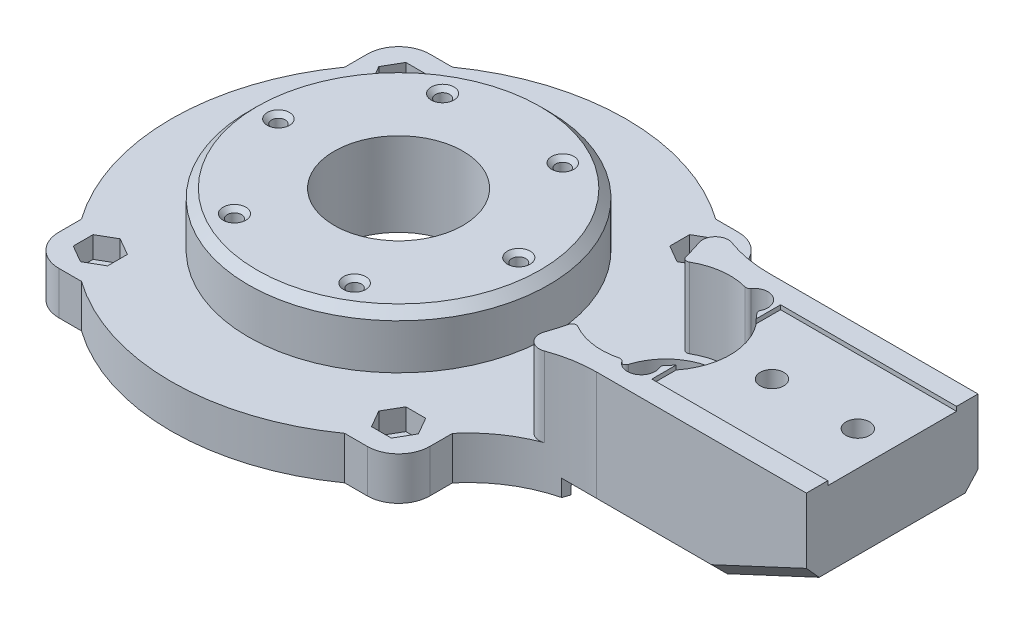
SolidWorks part; units mm, degrees
ref_plane "Front Plane" through (0, 0, 0) normal (0, 0, 1) x (1, 0, 0)
ref_plane "Top Plane" through (0, 0, 0) normal (0, 1, 0) x (1, 0, 0)
ref_plane "Right Plane" through (0, 0, 0) normal (1, 0, 0) x (0, 0, -1)
sketch "Sketch3" plane through (0, 0, 0) normal (0, -1, 0) x (1, 0, 0)
  line L1 (-28.2, -28.2) -> (28.2, -28.2) construction
  line L2 (-28.2, -28.2) -> (-28.2, 28.2) construction
  line L3 (-28.2, 28.2) -> (28.2, 28.2) construction
  line L4 (28.2, -28.2) -> (28.2, 28.2) construction
  line L5 (-28.2, -28.2) -> (28.2, 28.2) construction
  line L6 (-28.2, 28.2) -> (28.2, -28.2) construction
  circle A0 centre (0, 0) radius 62.5
  point P0 (0, 0)
  dimension "D2" = 125
  dimension "D1" = 56.4
extrude "Boss-Extrude3" add sketch "Sketch3" along normal blind 10
sketch "Sketch19" plane through (0, -10, 0) normal (0, -1, 0) x (1, 0, 0)
  line L0 (62.5, 0) -> (115, 0) construction
  line L1 (59.2136, -20) -> (115, -20)
  line L2 (59.2136, 20) -> (115, 20)
  line L3 (115, 20) -> (115, -20)
  line L4 (0, 20) -> (115, 20) construction
  line L5 (0, 0) -> (115, 0) construction
  line L6 (0, -20) -> (115, -20) construction
  circle A0 centre (0, 0) radius 62.5 construction
  arc A1 (59.2136, -20) -> (59.2136, 20) centre (0, 0) ccw
  dimension "D3" = 115
  dimension "D1" = 20
  dimension "D2" = 20
extrude "Boss-Extrude4" add sketch "Sketch19" against normal up to surface (10 mm away) up to face at (0, 0, -62.5)
sketch "Sketch20" plane through (0, 0, 0) normal (0, 1, 0) x (1, 0, 0)
  line L0 (0, 0) -> (119.1554, 0) construction
  line L6 (51.2348, -20) -> (115, -20)
  line L7 (115, -20) -> (115, 20)
  line L8 (115, 20) -> (51.2348, 20)
  arc A0 (51.2348, -20) -> (51.2348, 20) centre (0, 0) ccw
  dimension "D1" = 110
  dimension "D2" = 40
  dimension "D3" = 115
extrude "Boss-Extrude5" add sketch "Sketch20" along normal blind 18.5
chamfer "Chamfer1" distance 10 angle 65 1 edges at (115, -10, 0) first distance on face at (115, 4.25, 0)
sketch "Sketch21" plane through (0, -10, 0) normal (0, -1, 0) x (1, 0, 0)
  line L0 (115, 0) -> (0, 0) construction
  line L2 (115, 20) -> (115, -20) construction
  circle A0 centre (0, 0) radius 51 construction
  circle A1 centre (62.25, 0) radius 11.25 construction
  circle A2 centre (62.25, 0) radius 13
  dimension "D1" = 102
  dimension "D2" = 22.5
  dimension "D3" = 26
extrude "Cut-Extrude12" cut sketch "Sketch21" against normal blind 66
sketch "Sketch24" plane through (0, -10, 0) normal (0, -1, 0) x (1, 0, 0)
  circle A1 centre (62.25, 0) radius 13
  circle A2 centre (62.25, 0) radius 13
  dimension "D1" = 0
sketch "Sketch25" plane through (115, 0, 0) normal (1, 0, 0) x (0, 0, -1)
  line L0 (-20, 18.5) -> (20, 18.5) construction
  line L1 (15, 19.5) -> (-15, 19.5)
  line L2 (15, 19.5) -> (15, 17.5)
  line L3 (15, 17.5) -> (-15, 17.5)
  line L4 (-15, 19.5) -> (-15, 17.5)
  line L5 (15, 19.5) -> (-15, 17.5) construction
  line L6 (15, 17.5) -> (-15, 19.5) construction
  point P0 (0, 18.5)
  dimension "D1" = 2
  dimension "D2" = 30
extrude "Cut-Extrude14" cut sketch "Sketch25" against normal blind 41
sketch "Sketch26" plane through (0, -10, 0) normal (0, -1, 0) x (1, 0, 0)
  line L0 (115, 0) -> (0, 0) construction
  line L1 (115, 20) -> (115, -20) construction
  circle A0 centre (107, 0) radius 2.75
  circle A1 centre (87, 0) radius 2.75
  dimension "D3" = 5.5
  dimension "D1" = 8
  dimension "D2" = 20
extrude "Cut-Extrude15" cut sketch "Sketch26" against normal through all
sketch "Sketch27" plane through (0, -10, 0) normal (0, -1, 0) x (1, 0, 0)
  circle A0 centre (87, 0) radius 4.6
  circle A1 centre (107, 0) radius 4.6
  dimension "D1" = 9.2
extrude "Cut-Extrude16" cut sketch "Sketch27" against normal blind 14
chamfer "Chamfer3" distance 3 angle 45 4 edges at (104.2775, -5, -20) (76.3843, -10, -20) (104.2775, -5, 20) (76.3843, -10, 20)
sketch "Sketch43" plane through (0, -15, 0) normal (0, -1, 0) x (1, 0, 0)
  line L0 (62.25, 0) -> (47.2509, -0.1631) construction
  line L1 (62.25, 0) -> (69.6081, 13.0713) construction
  line L2 (62.25, 0) -> (69.8908, -12.9081) construction
  circle A0 centre (47.2509, -0.1631) radius 1.75
  circle A1 centre (69.6081, 13.0713) radius 1.75
  circle A2 centre (69.8908, -12.9081) radius 1.75
  circle A3 centre (62.25, 0) radius 15 construction
  dimension "D1" = 3.5
  dimension "D2" = 30
  dimension "D3" = 120.001
  dimension "D4" = 120
extrude "Cut-Extrude22" cut sketch "Sketch43" against normal blind 42
sketch "Sketch44" plane through (0, 0, 0) normal (0, 1, 0) x (1, 0, 0)
  circle A0 centre (69.8908, 12.9081) radius 3
  dimension "D1" = 6
extrude "Cut-Extrude23" cut sketch "Sketch44" against normal blind 5
sketch "Sketch49" plane through (0, 18.5, 0) normal (0, 1, 0) x (1, 0, 0)
  circle A0 centre (69.6081, -13.0713) radius 3.25
  circle A1 centre (47.2509, 0.1631) radius 3.25
  circle A2 centre (69.8908, 12.9081) radius 3.25
  dimension "D1" = 6.5
extrude "Cut-Extrude28" cut sketch "Sketch49" against normal blind 23
fillet "Fillet4" radius 1 2 edges at (49.4953, -2.25, -2.5136) (49.4437, -2.25, 2.2357)
chamfer "Chamfer6" distance 1 angle 45 3 edges at (69.8908, -5, -11.1581) (47.2509, -4.5, 1.5869) (69.6081, -4.5, 14.8213)
sketch "Sketch52" plane through (0, 18.5, 0) normal (0, 1, 0) x (1, 0, 0)
  circle A1 centre (0, 0) radius 49
  dimension "D1" = 98
sketch "Sketch53" plane through (0, 0, 0) normal (0, 1, 0) x (1, 0, 0)
  circle A0 centre (0, 0) radius 35
  dimension "D1" = 70
extrude "Boss-Extrude7" add sketch "Sketch53" along normal blind 12.5
sketch "Sketch54" plane through (0, -10, 0) normal (0, -1, 0) x (1, 0, 0)
  line L1 (-34.75, 34.75) -> (34.75, 34.75) construction
  line L2 (-34.75, 34.75) -> (-34.75, -34.75) construction
  line L3 (-34.75, -34.75) -> (34.75, -34.75) construction
  line L4 (34.75, 34.75) -> (34.75, -34.75) construction
  line L5 (-34.75, 34.75) -> (34.75, -34.75) construction
  line L6 (-34.75, -34.75) -> (34.75, 34.75) construction
  circle A0 centre (-34.75, 34.75) radius 2.75
  circle A1 centre (34.75, 34.75) radius 2.75
  circle A2 centre (34.75, -34.75) radius 2.75
  circle A3 centre (-34.75, -34.75) radius 2.75
  point P0 (0, 0)
  dimension "D2" = 5.5
  dimension "D1" = 69.5
extrude "Cut-Extrude29" cut sketch "Sketch54" against normal through all
chamfer "Chamfer7" distance 2 angle 45 1 edges at (0, 12.5, 35)
sketch "Sketch56" plane through (0, -10, 0) normal (0, -1, 0) x (1, 0, 0)
  line L2 (-35.925, -42.925) -> (35.925, -42.925)
  line L6 (42.925, -35.925) -> (42.925, 35.925)
  line L10 (35.925, 42.925) -> (-35.925, 42.925)
  line L14 (-42.925, 35.925) -> (-42.925, -35.925)
  circle A0 centre (0, 0) radius 37
  circle A1 centre (-34.75, 34.75) radius 2.75
  circle A2 centre (34.75, 34.75) radius 2.75
  circle A3 centre (-34.75, -34.75) radius 2.75
  circle A4 centre (34.75, -34.75) radius 2.75
  arc A5 (-42.925, -35.925) -> (-35.925, -42.925) centre (-35.925, -35.925) ccw
  arc A7 (35.925, -42.925) -> (42.925, -35.925) centre (35.925, -35.925) ccw
  arc A9 (42.925, 35.925) -> (35.925, 42.925) centre (35.925, 35.925) ccw
  arc A11 (-35.925, 42.925) -> (-42.925, 35.925) centre (-35.925, 35.925) ccw
  dimension "D1" = 74
sketch "Sketch57" plane through (0, -10, 0) normal (0, -1, 0) x (1, 0, 0)
  line L0 (35.925, 42.925) -> (-35.925, 42.925) construction
  line L1 (-42.925, 35.925) -> (-42.925, -35.925) construction
  line L2 (42.925, -35.925) -> (42.925, 35.925) construction
  line L3 (60.1436, -17) -> (93.5549, -17)
  line L4 (93.5549, -17) -> (93.5549, 17)
  line L5 (93.5549, 17) -> (60.1436, 17)
  line L7 (93.5549, -17) -> (93.5549, 17)
  line L8 (93.5549, 17) -> (60.1436, 17)
  line L9 (-35.925, -42.925) -> (35.925, -42.925) construction
  line L10 (35.925, 42.925) -> (-35.925, 42.925) construction
  line L11 (-42.925, 35.925) -> (-42.925, -35.925) construction
  line L12 (42.925, -35.925) -> (42.925, 35.925) construction
  line L13 (-35.925, -42.925) -> (35.925, -42.925) construction
  line L14 (35.925, 43.225) -> (-35.925, 43.225)
  line L15 (-43.225, 35.925) -> (-43.225, -35.925)
  line L16 (-35.925, -43.225) -> (35.925, -43.225)
  line L17 (43.225, -35.925) -> (43.225, 35.925)
  line L21 (60.1436, -17) -> (93.5549, -17)
  arc A0 (-35.925, 42.925) -> (-42.925, 35.925) centre (-35.925, 35.925) ccw construction
  arc A1 (-42.925, -35.925) -> (-35.925, -42.925) centre (-35.925, -35.925) ccw construction
  arc A2 (35.925, -42.925) -> (42.925, -35.925) centre (35.925, -35.925) ccw construction
  arc A3 (60.1436, 17) -> (60.1436, -17) centre (0, 0) ccw
  arc A4 (60.1436, 17) -> (60.1436, -17) centre (0, 0) ccw
  arc A9 (-35.925, 42.925) -> (-42.925, 35.925) centre (-35.925, 35.925) ccw construction
  arc A10 (-42.925, -35.925) -> (-35.925, -42.925) centre (-35.925, -35.925) ccw construction
  arc A11 (35.925, -42.925) -> (42.925, -35.925) centre (35.925, -35.925) ccw construction
  arc A12 (42.925, 35.925) -> (35.925, 42.925) centre (35.925, 35.925) ccw construction
  arc A13 (42.925, 35.925) -> (35.925, 42.925) centre (35.925, 35.925) ccw construction
  arc A14 (-35.925, 43.225) -> (-43.225, 35.925) centre (-35.925, 35.925) ccw
  arc A15 (-43.225, -35.925) -> (-35.925, -43.225) centre (-35.925, -35.925) ccw
  arc A16 (35.925, -43.225) -> (43.225, -35.925) centre (35.925, -35.925) ccw
  arc A17 (43.225, 35.925) -> (35.925, 43.225) centre (35.925, 35.925) ccw
  dimension "D1" = 0
  dimension "D2" = 0.3
sketch "Sketch61" plane through (0, 0, 0) normal (0, 1, 0) x (1, 0, 0)
  circle A0 centre (34.75, -34.75) radius 5.5
  circle A1 centre (-34.75, -34.75) radius 5.5
  circle A2 centre (-34.75, 34.75) radius 5.5
  circle A3 centre (34.75, 34.75) radius 5.5
  dimension "D1" = 11
fillet "Fillet6" radius 1 4 edges at (70.8042, 7, -9.789) (66.717, 7, -12.2084) (70.5891, 7, 9.9729) (66.4502, 7, 12.3028)
sketch "Sketch66" plane through (0, 18.5, 0) normal (0, 1, 0) x (1, 0, 0)
  circle A0 centre (62.25, 0) radius 15
  dimension "D1" = 30
extrude "Cut-Extrude39" cut sketch "Sketch66" against normal up to surface (18.5 mm away) up to face at (-34.75, 0, -37.5)
sketch "Sketch67" plane through (0, -10, 0) normal (0, -1, 0) x (1, 0, 0)
  line L4 (-35.925, -43.225) -> (-30.6692, -43.225)
  line L5 (43.225, -35.925) -> (43.225, -30.6692)
  line L6 (35.925, 43.225) -> (30.6692, 43.225)
  line L7 (-43.225, 35.925) -> (-43.225, 30.6692)
  line L8 (-30.6692, 43.225) -> (-35.925, 43.225)
  line L9 (-43.225, -30.6692) -> (-43.225, -35.925)
  line L10 (30.6692, -43.225) -> (35.925, -43.225)
  line L11 (43.225, 30.6692) -> (43.225, 35.925)
  line L12 (59.2136, -20) -> (49.0816, -20)
  line L13 (51.2348, 20) -> (49.0816, 20)
  line L19 (115, 20) -> (51.2348, 20)
  line L20 (115, 15) -> (115, 20)
  line L21 (74, 15) -> (115, 15)
  line L22 (74, 9.324) -> (74, 15)
  line L26 (59.2136, 20) -> (51.2348, 20)
  arc A0 (-43.225, 30.6692) -> (-43.225, -30.6692) centre (0, 0) ccw
  arc A5 (-43.225, -35.925) -> (-35.925, -43.225) centre (-35.925, -35.925) ccw
  arc A6 (35.925, -43.225) -> (43.225, -35.925) centre (35.925, -35.925) ccw
  arc A7 (43.225, 35.925) -> (35.925, 43.225) centre (35.925, 35.925) ccw
  arc A8 (-35.925, 43.225) -> (-43.225, 35.925) centre (-35.925, 35.925) ccw
  arc A9 (43.225, -30.6692) -> (49.0816, -20) centre (0, 0) ccw
  arc A10 (-30.6692, -43.225) -> (30.6692, -43.225) centre (0, 0) ccw
  arc A11 (30.6692, 43.225) -> (-30.6692, 43.225) centre (0, 0) ccw
  arc A12 (59.2136, 20) -> (59.2136, -20) centre (0, 0) ccw construction
  arc A13 (59.2136, 20) -> (59.2136, -20) centre (0, 0) ccw
  arc A14 (49.0816, 20) -> (43.225, 30.6692) centre (0, 0) ccw
  arc A19 (74, 9.324) -> (72.2508, 11.1796) centre (62.25, 0) ccw
  arc A22 (72.2508, 11.1796) -> (66.6199, 14.3494) centre (69.6081, 13.0713) ccw
  arc A23 (66.6199, 14.3494) -> (53.615, 12.2652) centre (62.25, 0) ccw
  arc A24 (53.615, 12.2652) -> (51.2348, 20) centre (0, 0) ccw
  point P28 (58.3572, -20)
  point P30 (0, 0)
  dimension "D1" = 0
extrude "Cut-Extrude40" cut sketch "Sketch67" against normal through all
fillet "Fillet8" radius 30 2 edges at (49.0816, -5, 20) (49.0816, -5, -20)
fillet "Fillet9" radius 3 2 edges at (48.6585, 9.25, 25.6389) (48.6585, 9.25, -25.6389)
fillet "Fillet10" radius 1 6 edges at (72.4918, 9.25, -10.9593) (66.9312, 9.25, -14.2508) (53.615, 9.25, -12.2652) (53.615, 9.25, 12.2652) (66.6199, 9.25, 14.3494) (72.2508, 9.25, 11.1796)
sketch "Sketch68" plane through (0, -10, 0) normal (0, -1, 0) x (1, 0, 0)
  circle A0 centre (62.25, 0) radius 19.5
  dimension "D1" = 39
extrude "Cut-Extrude41" cut sketch "Sketch68" against normal blind 2
sketch "Sketch70" plane through (0, -10, 0) normal (0, -1, 0) x (1, 0, 0)
  circle A1 centre (0, 0) radius 37
  circle A2 centre (0, 0) radius 37
  dimension "D1" = 0
extrude "Cut-Extrude42" cut sketch "Sketch70" against normal blind 3
sketch "Sketch71" plane through (0, -10, 0) normal (0, -1, 0) x (1, 0, 0)
  circle A0 centre (0, 0) radius 15
extrude "Cut-Extrude43" cut sketch "Sketch71" against normal through all
sketch "Sketch73" plane through (0, 12.5, 0) normal (0, 1, 0) x (1, 0, 0)
  circle A0 centre (0, 0) radius 28 construction
  circle A1 centre (-28, 0) radius 1.6
  circle A2 centre (14, 24.2487) radius 1.6
  circle A3 centre (14, -24.2487) radius 1.6
  point P12 (0, 0)
  dimension "D1" = 56
  dimension "D2" = 3.2
  dimension "D3" = 3
extrude "Cut-Extrude44" cut sketch "Sketch73" against normal blind 6
sketch "Sketch74" plane through (0, 12.5, 0) normal (0, 1, 0) x (1, 0, 0)
  line L0 (0, 0) -> (-19.4633, 33.7115) construction
  line L1 (0, 0) -> (-28, 0) construction
  circle A0 centre (0, 0) radius 28 construction
  circle A1 centre (-14, 24.2487) radius 1.65
  point P8 (0, 0)
  dimension "D2" = 3.3
  dimension "D1" = 60
extrude "Cut-Extrude45" cut sketch "Sketch74" against normal through all
sketch "Sketch75" plane through (0, -10, 0) normal (0, -1, 0) x (1, 0, 0)
  line L1 (-15.5484, -27.0211) -> (-12.3733, -26.9758)
  line L2 (-12.3733, -26.9758) -> (-10.8249, -24.2035)
  line L3 (-10.8249, -24.2035) -> (-12.4516, -21.4764)
  line L4 (-12.4516, -21.4764) -> (-15.6267, -21.5216)
  line L5 (-15.6267, -21.5216) -> (-17.1751, -24.294)
  line L6 (-17.1751, -24.294) -> (-15.5484, -27.0211)
  circle A0 centre (-14, -24.2487) radius 2.75 construction
  dimension "D1" = 5.5
extrude "Cut-Extrude46" cut sketch "Sketch75" against normal blind 14
pattern_circular "CirPattern1" count 3 over 360 about axis through (0, -7, 0) along (0, -1, 0) of "Cut-Extrude46", "Cut-Extrude45"
chamfer "Chamfer8" distance 1 angle 45 6 edges at (-12.5711, 12.5, 23.4237) (-28, 12.5, 1.6) (-14, 12.5, -22.5987) (14, 12.5, -22.6487) (26.5711, 12.5, -0.825) (14, 12.5, 25.8487)
sketch "Sketch76" plane through (0, 0, 0) normal (0, 1, 0) x (1, 0, 0)
  line L1 (-34.75, -39.3688) -> (-30.75, -37.0594)
  line L2 (-30.75, -37.0594) -> (-30.75, -32.4406)
  line L3 (-30.75, -32.4406) -> (-34.75, -30.1312)
  line L4 (-34.75, -30.1312) -> (-38.75, -32.4406)
  line L5 (-38.75, -32.4406) -> (-38.75, -37.0594)
  line L6 (-38.75, -37.0594) -> (-34.75, -39.3688)
  circle A0 centre (-34.75, -34.75) radius 4 construction
  dimension "D1" = 8
extrude "Cut-Extrude47" cut sketch "Sketch76" against normal blind 5
pattern_circular "CirPattern2" count 4 over 360 about axis through (0, 12.5, 0) along (0, 1, 0) of "Cut-Extrude47"
chamfer "Chamfer9" distance 1 angle 45 4 edges at (34.75, -10, -37.5) (34.75, -10, 32) (-34.75, -10, 32) (-34.75, -10, -37.5)
